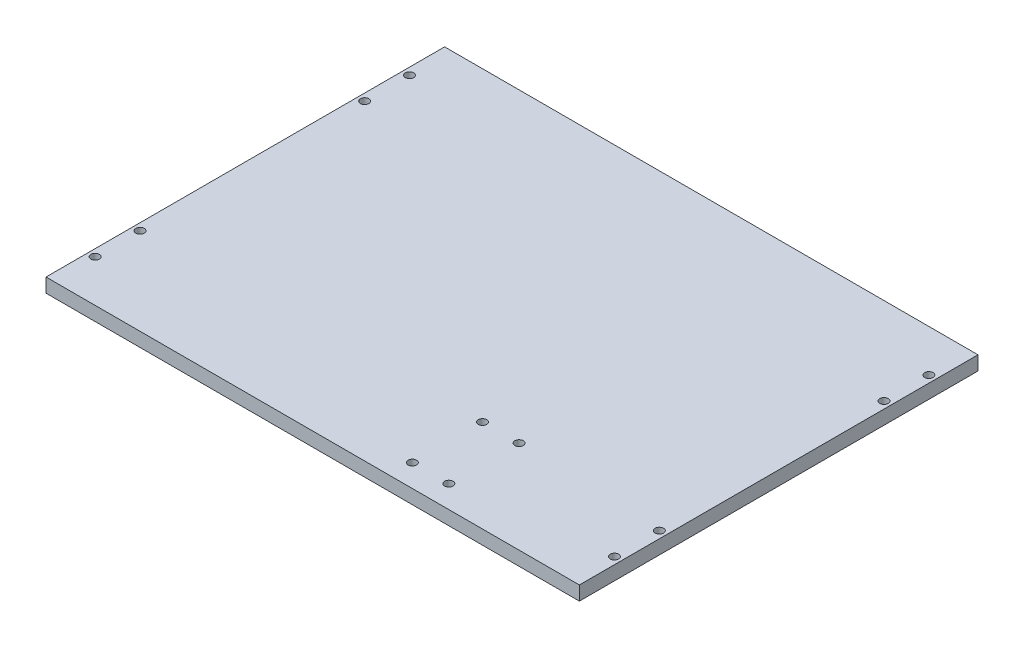
SolidWorks part; units mm, degrees
ref_plane "Front Plane" through (0, 0, 0) normal (0, 0, 1) x (1, 0, 0)
ref_plane "Top Plane" through (0, 0, 0) normal (0, 1, 0) x (1, 0, 0)
ref_plane "Right Plane" through (0, 0, 0) normal (1, 0, 0) x (0, 0, -1)
sketch "Sketch1" plane through (0, 0, 0) normal (0, 1, 0) x (1, 0, 0)
  line L1 (0, 0) -> (95, 0)
  line L2 (0, 0) -> (0, 142)
  line L3 (0, 142) -> (95, 142)
  line L4 (95, 0) -> (95, 142)
  circle A0 centre (92.5, 15) radius 1.5
  circle A2 centre (92.5, 31) radius 1.5
  circle A3 centre (92.5, 127) radius 1.5
  circle A5 centre (92.5, 111) radius 1.5
  dimension "D4" = 3
  dimension "D5" = 3
  dimension "D12" = 3
  dimension "D14" = 3
  dimension "D1" = 95
  dimension "D2" = 142
  dimension "D6" = 2.5
  dimension "D8" = 2.5
  dimension "D9" = 15
  dimension "D10" = 31
  dimension "D15" = 15
  dimension "D16" = 31
extrude "Boss-Extrude1" add sketch "Sketch1" along normal blind 5
mirror "Mirror1" about plane through (0, 5, 0) normal (1, 0, 0) of "Boss-Extrude1"
sketch "Sketch2" plane through (0, 5, 0) normal (0, 1, 0) x (1, 0, 0)
  line L0 (-95, 0) -> (95, 0) construction
  line L1 (95, 0) -> (95, 142) construction
  circle A0 centre (27.5, 8) radius 1.5
  circle A1 centre (27.5, 33) radius 1.5
  dimension "D1" = 3
  dimension "D2" = 3
  dimension "D3" = 8
  dimension "D4" = 33
  dimension "D5" = 67.5
  dimension "D6" = 67.5
extrude "Cut-Extrude1" cut sketch "Sketch2" against normal up to next
sketch "Sketch3" plane through (0, 5, 0) normal (0, 1, 0) x (1, 0, 0)
  line L0 (95, 0) -> (95, 142) construction
  line L1 (-95, 0) -> (95, 0) construction
  circle A0 centre (40.5, 33) radius 1.5
  circle A1 centre (40.5, 8) radius 1.5
  dimension "D1" = 3
  dimension "D2" = 3
  dimension "D3" = 54.5
  dimension "D4" = 54.5
  dimension "D5" = 8
  dimension "D6" = 33
extrude "Cut-Extrude2" cut sketch "Sketch3" against normal up to next
